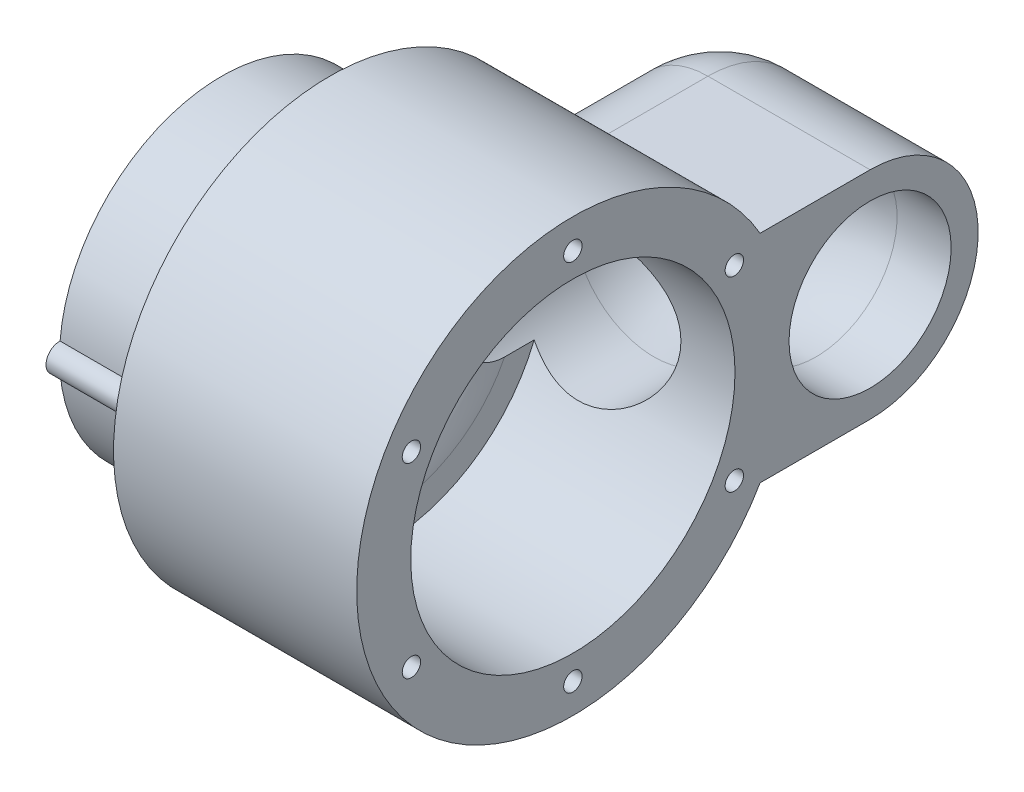
SolidWorks part; units mm, degrees
material "ABS"
ref_plane "Front" through (0, 0, 0) normal (0, 0, 1) x (1, 0, 0)
ref_plane "Top" through (0, 0, 0) normal (0, 1, 0) x (1, 0, 0)
ref_plane "Right" through (0, 0, 0) normal (1, 0, 0) x (0, 0, -1)
sketch "Croquis1" plane through (0, 0, 0) normal (1, 0, 0) x (0, 0, -1)
  arc A0 (-29.8958, -2.4978) -> (-29.8958, 2.4978) centre (0, 0) ccw
  arc A1 (-29.8958, 2.4978) -> (-29.8958, -2.4978) centre (-30, 0) ccw
  circle A2 centre (0, 0) radius 15
  dimension "D1" = 60
  dimension "D2" = 5
  dimension "D3" = 30
extrude "Saliente-Extruir1" add sketch "Croquis1" along normal mid plane 20
sketch "Croquis2" plane through (10, 0, 0) normal (1, 0, 0) x (0, 0, -1)
  circle A0 centre (0, 0) radius 40
  circle A1 centre (0, 0) radius 15
  dimension "D1" = 80
  dimension "D2" = 30
extrude "Saliente-Extruir2" add sketch "Croquis2" along normal blind 10
sketch "Croquis3" plane through (20, 0, 0) normal (1, 0, 0) x (0, 0, -1)
  circle A0 centre (0, 0) radius 40 construction
  circle A1 centre (0, 0) radius 40
  circle A2 centre (0, 0) radius 30
  dimension "D1" = 60
extrude "Saliente-Extruir3" add sketch "Croquis3" along normal blind 35
hole_wizard "Refrentado para tornillo con cabeza troncocónica de M31" positions "Croquis4" profile "Croquis6" counterbore size "M3" standard "Ansi Metric" end condition up to next
sketch "Croquis4" plane through (10, 0, 0) normal (-1, 0, 0) x (0, 0, 1)
  line L0 (0, -35.75) -> (0, 35.75) construction
  point P0 (0, 34.5)
  point P11 (29.8779, 17.25)
  point P12 (29.8779, -17.25)
  point P13 (0, -34.5)
  point P14 (-29.8779, -17.25)
  point P15 (-29.8779, 17.25)
  dimension "D1" = 34.5
  dimension "D2" = 6
sketch "Croquis6" plane through (10, 34.5, 0) normal (0, 1, 0) x (0, 0, 1)
  line L0 (0, 0) -> (0, 45)
  line L1 (0, 45) -> (1.7, 45)
  line L3 (1.7, 45) -> (1.7, 2.4)
  line L4 (1.7, 2.4) -> (3.5, 2.4)
  line L5 (3.5, 2.4) -> (3.5, 0)
  line L7 (3.5, 0) -> (0, 0)
  line L11 (0, -6.35) -> (0, 107.95) construction
  dimension "Diámetro de taladro hasta el siguiente" = 3.4
  dimension "Profundidad de taladro hasta el siguiente" = 45
  dimension "Diámetro de refrentado" = 7
  dimension "Profundidad de refrentado" = 2.4
sketch "Croquis8" plane through (55, 0, 0) normal (1, 0, 0) x (0, 0, -1)
  line L3 (55, 0) -> (40, 0) construction
  line L4 (55, 20) -> (34.641, 20)
  line L5 (55, -20) -> (34.641, -20)
  arc A3 (55, -20) -> (55, 20) centre (55, 0) ccw
  circle A4 centre (0, 0) radius 40 construction
  arc A5 (34.641, -20) -> (34.641, 20) centre (0, 0) ccw
  dimension "D1" = 40
  dimension "D2" = 15
extrude "Saliente-Extruir4" add sketch "Croquis8" against normal up to surface (45 mm away) up to face at (10, 34.5, 3.5)
fillet "Redondeo1" radius 15 3 edges at (10, 20, -44.8205) (10, -20, -44.8205) (10, 0, -75)
sketch "Croquis17" plane through (0, 0, 0) normal (0, 1, 0) x (1, 0, 0)
  line L0 (55, 55) -> (45, 55)
  line L1 (25, 55) -> (55, 55) construction
  line L2 (30, 40) -> (30, 0)
  line L3 (-35.75, 0) -> (35.75, 0) construction
  line L4 (10, 39.6863) -> (10, 55) construction
  arc A0 (45, 55) -> (30, 40) centre (45, 40) ccw
  point P12 (30, 55)
  dimension "D2" = 15
  dimension "D1" = 20
sweep "Cortar-Barrer4" cut path "Croquis17" circular profile diameter 30 parameters "D3"=30
fillet "Redondeo2" radius 10 1 edges at (20, 0, 15)
